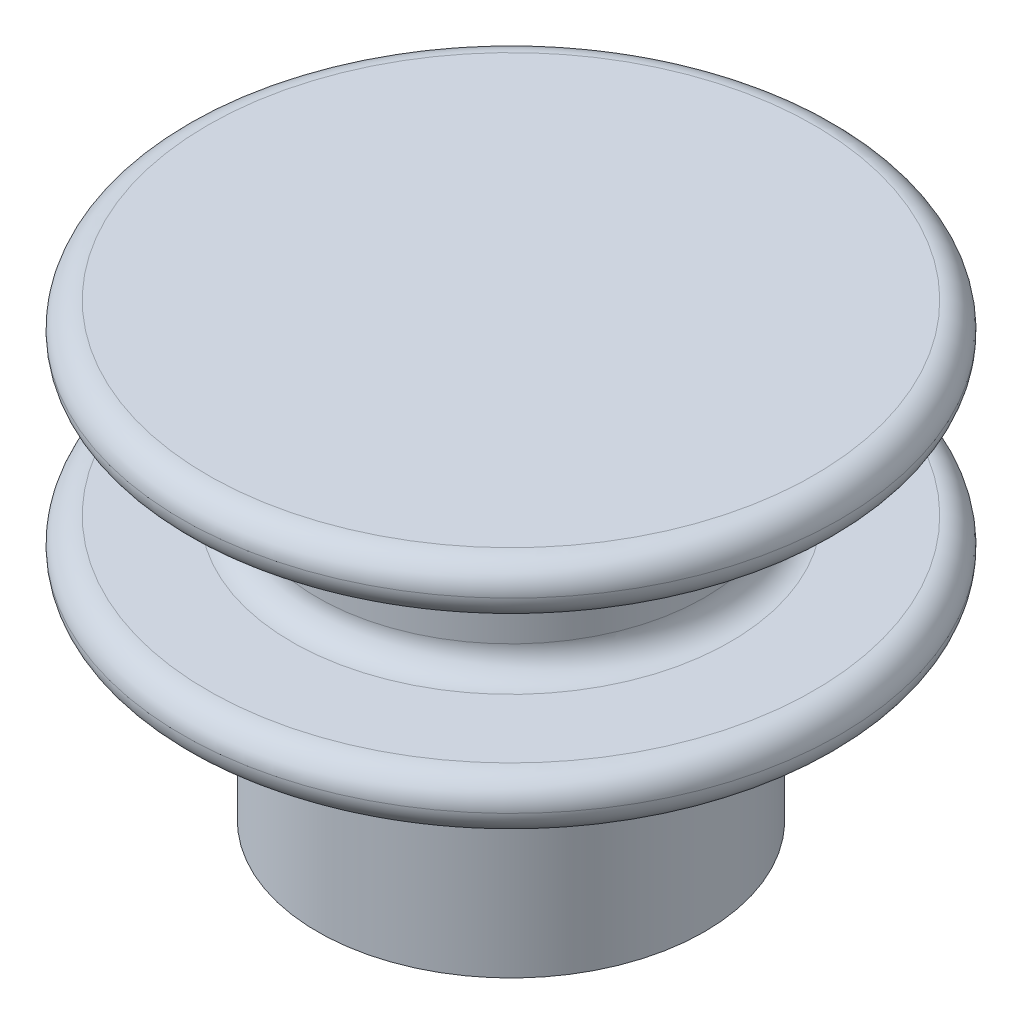
SolidWorks part; units mm, degrees
ref_plane "Front Plane" through (0, 0, 0) normal (0, 0, 1) x (1, 0, 0)
ref_plane "Top Plane" through (0, 0, 0) normal (0, 1, 0) x (1, 0, 0)
ref_plane "Right Plane" through (0, 0, 0) normal (1, 0, 0) x (0, 0, -1)
sketch "Sketch2" plane through (0, 0, 0) normal (0, 0, 1) x (1, 0, 0)
  line L0 (0, 0) -> (6, 0) construction
  line L2 (0, 3.683) -> (10.191, 3.683)
  line L3 (10.191, 3.683) -> (10.191, 2.0955)
  line L4 (10.191, 2.0955) -> (6, 2.0955)
  line L5 (6, 2.0955) -> (6, -2.0955)
  line L6 (6, -2.0955) -> (10.191, -2.0955)
  line L7 (10.191, -2.0955) -> (10.191, -3.683)
  line L8 (10.191, -3.683) -> (0, -3.683)
  line L9 (0, -3.683) -> (0, 3.683)
  point P1 (0, 0)
  point P17 (6, 0)
  dimension "D1" = 4.191
  dimension "D2" = 4.191
  dimension "D3" = 6
  dimension "D4" = 1.5875
revolve "Revolve1" add sketch "Sketch2" angle 360 about L9
sketch "Sketch7" plane through (0, -3.683, 0) normal (0, -1, 0) x (-1, 0, 0)
  circle A0 centre (0, 0) radius 6.5
  dimension "D1" = 13
extrude "Boss-Extrude2" add sketch "Sketch7" along normal blind 1.5875
fillet "Fillet1" radius 0.7937 7 edges at (6, -2.0955, 0) (6, 2.0955, 0) (10.191, 3.683, 0) (10.191, 2.0955, 0) (10.191, -3.683, 0) (10.191, -2.0955, 0) (6.5, -3.683, 0)
sketch "Sketch6" plane through (0, -5.2705, 0) normal (0, -1, 0) x (1, 0, 0)
  circle A0 centre (0, 0) radius 6
  dimension "D1" = 12
extrude "Boss-Extrude1" add sketch "Sketch6" along normal blind 5
sketch "Sketch5" plane through (0, -10.2705, 0) normal (0, -1, 0) x (1, 0, 0)
  line L0 (-1.7145, 0) -> (1.7145, 0) construction
  circle A0 centre (-1.7145, 0) radius 1.651
  circle A1 centre (1.7145, 0) radius 1.651
  point P4 (0, 0)
  dimension "D2" = 3.302
  dimension "D1" = 3.429
extrude "Cut-Extrude3" cut sketch "Sketch5" against normal blind 8.89
